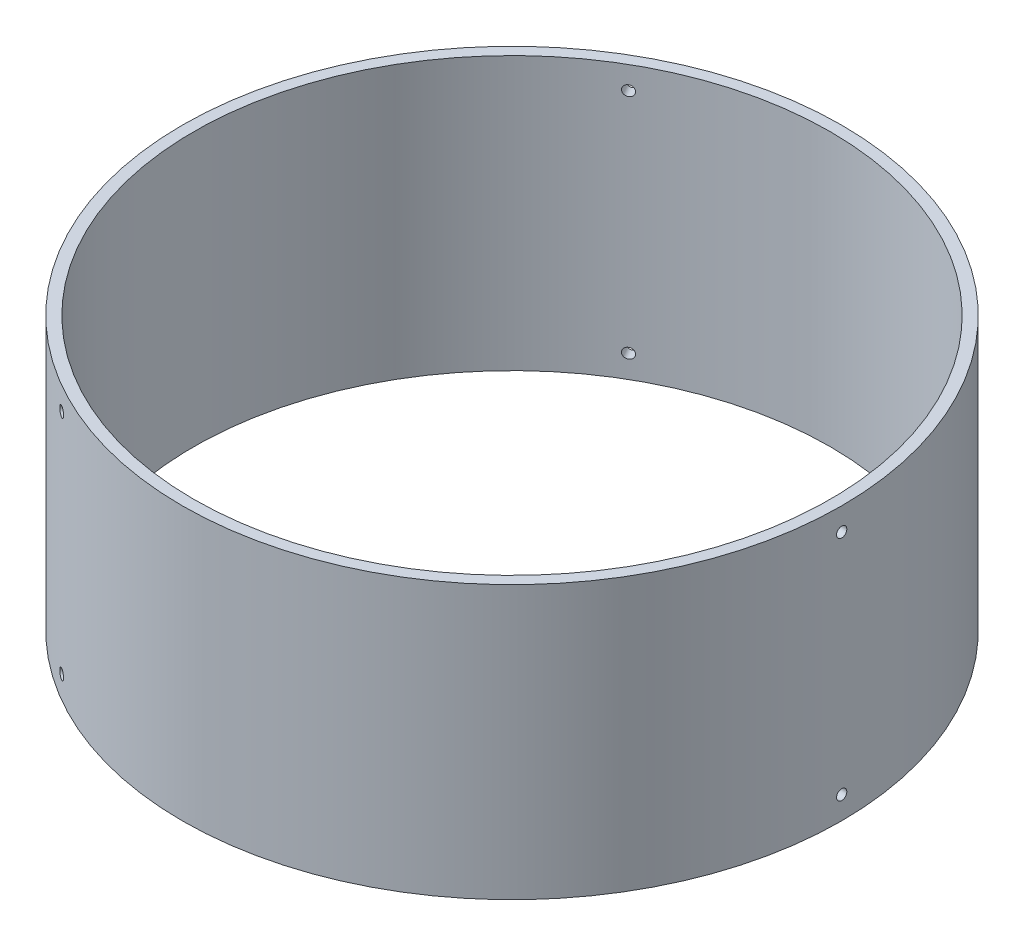
SolidWorks part; units mm, degrees
material "Acrylic (Medium-high impact)"
ref_plane "Front Plane" through (0, 0, 0) normal (0, 0, 1) x (1, 0, 0)
ref_plane "Top Plane" through (0, 0, 0) normal (0, 1, 0) x (1, 0, 0)
ref_plane "Right Plane" through (0, 0, 0) normal (1, 0, 0) x (0, 0, -1)
sketch "Sketch1" plane through (0, 0, 0) normal (0, 1, 0) x (1, 0, 0)
  circle A0 centre (0, 0) radius 92.075
  circle A1 centre (0, 0) radius 88.9
  dimension "D1" = 184.15
  dimension "D2" = 177.8
extrude "Boss-Extrude1" add sketch "Sketch1" along normal mid plane 76.2
ref_plane "Plane1" through (92.075, 0, 0) normal (1, 0, 0) x (0, 0, -1)
sketch "Sketch3" plane through (92.075, 0, 0) normal (1, 0, 0) x (0, 0, -1)
  line L0 (0, 103.0288) -> (0, -103.0288) construction
  line L1 (88.9, 38.1) -> (-88.9, 38.1) construction
  line L2 (-92.075, -38.1) -> (92.075, -38.1) construction
  circle A0 centre (0, -31.75) radius 1.4351
  circle A1 centre (0, 31.75) radius 1.4351
  dimension "D1" = 6.35
  dimension "D2" = 2.8702
  dimension "D3" = 2.8702
  dimension "D4" = 6.35
extrude "Cut-Extrude1" cut sketch "Sketch3" against normal blind 34.798
pattern_circular "CirPattern1" count 3 over 360 about axis through (0, 38.1, 0) along (0, -1, 0) of "Cut-Extrude1"
